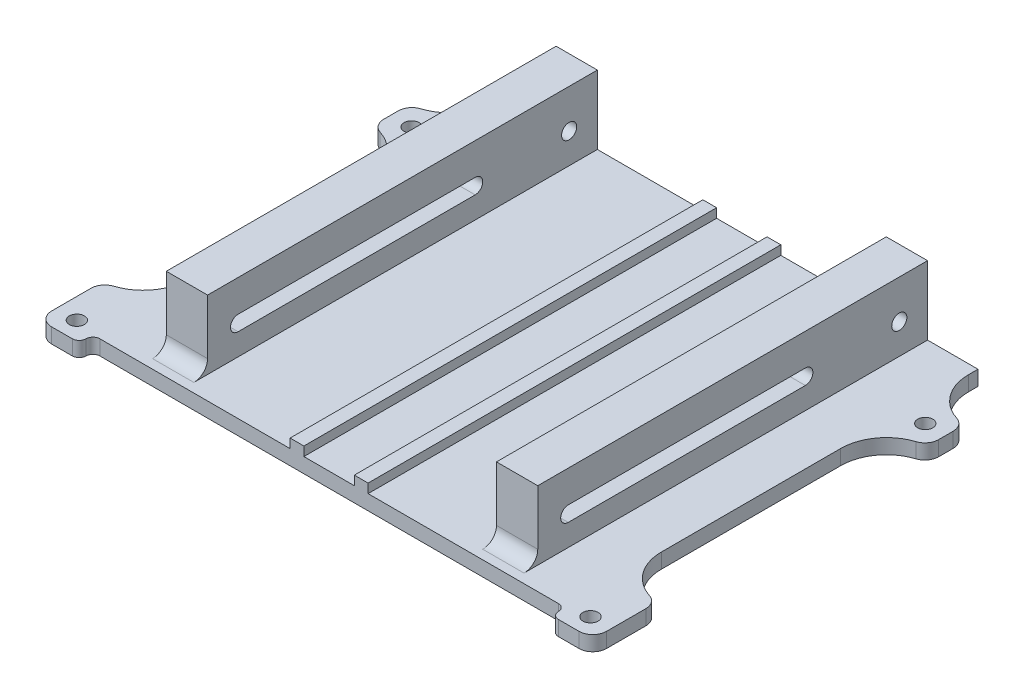
SolidWorks part; units mm, degrees
ref_plane "Front Plane" through (0, 0, 0) normal (0, 0, 1) x (1, 0, 0)
ref_plane "Top Plane" through (0, 0, 0) normal (0, 1, 0) x (1, 0, 0)
ref_plane "Right Plane" through (0, 0, 0) normal (1, 0, 0) x (0, 0, -1)
sketch "Sketch1" plane through (0, 0, 0) normal (0, 1, 0) x (1, 0, 0)
  line L1 (-51.5, 32.5) -> (51.5, 32.5)
  line L2 (-51.5, 32.5) -> (-51.5, -32.5)
  line L3 (-51.5, -32.5) -> (51.5, -32.5)
  line L4 (51.5, 32.5) -> (51.5, -32.5)
  line L5 (-51.5, 32.5) -> (51.5, -32.5) construction
  line L6 (-51.5, -32.5) -> (51.5, 32.5) construction
  point P0 (0, 0)
  dimension "D1" = 65
  dimension "D2" = 103
extrude "Boss-Extrude1" add sketch "Sketch1" along normal blind 3.25
sketch "Sketch2" plane through (0, 3.25, 0) normal (0, 1, 0) x (1, 0, 0)
  line L0 (-51.5, -32.5) -> (51.5, -32.5) construction
  line L1 (-40.5, 32.5) -> (-31.5, 32.5)
  line L2 (-40.5, 32.5) -> (-40.5, -32.5)
  line L3 (-40.5, -32.5) -> (-31.5, -32.5)
  line L4 (-31.5, 32.5) -> (-31.5, -32.5)
  dimension "D1" = 9
  dimension "D2" = 31.5
extrude "Boss-Extrude2" add sketch "Sketch2" along normal blind 15
sketch "Sketch3" plane through (-31.5, 0, 0) normal (1, 0, 0) x (0, 0, -1)
  line L0 (25.85, 9.65) -> (-25.85, 9.65) construction
  line L5 (25.85, 8) -> (-25.85, 8)
  line L6 (25.85, 11.3) -> (-25.85, 11.3)
  arc A4 (25.85, 8) -> (25.85, 11.3) centre (25.85, 9.65) ccw
  arc A5 (-25.85, 11.3) -> (-25.85, 8) centre (-25.85, 9.65) ccw
  point P2 (0, 9.65)
  point P9 (27.5, 11.3)
  point P12 (27.5, 8)
  point P17 (-27.5, 11.3)
  dimension "D4" = 51.7
  dimension "D1" = 3.3
  dimension "D2" = 55
  dimension "D3" = 3.3
extrude "Cut-Extrude1" cut sketch "Sketch3" against normal through all
sketch "Sketch4" plane through (0, 0, -32.5) normal (0, 0, -1) x (-1, 0, 0)
  line L8 (-51.5, 0) -> (51.5, 0)
  line L9 (51.5, 0) -> (51.5, 3.25)
  line L10 (40.5, 18.25) -> (31.5, 18.25)
  line L11 (31.5, 18.25) -> (31.5, 3.25)
  line L12 (31.5, 3.25) -> (-51.5, 3.25)
  line L13 (51.5, 3.25) -> (40.5, 3.25)
  line L14 (51.5, 3.25) -> (40.5, 3.25)
  line L15 (-51.5, 3.25) -> (-51.5, 0)
  line L16 (-51.5, 0) -> (51.5, 0)
  line L17 (51.5, 0) -> (51.5, 3.25)
  line L18 (40.5, 18.25) -> (31.5, 18.25)
  line L19 (31.5, 18.25) -> (31.5, 3.25)
  line L20 (31.5, 3.25) -> (-51.5, 3.25)
  line L23 (-51.5, 3.25) -> (-51.5, 0)
  line L24 (40.5, 3.25) -> (40.5, 18.25)
  line L25 (40.5, 3.25) -> (40.5, 18.25)
  dimension "D1" = 0
extrude "Boss-Extrude3" add sketch "Sketch4" along normal blind 20
sketch "Sketch5" plane through (-31.5, 0, 0) normal (1, 0, 0) x (0, 0, -1)
  line L0 (27.5, 9.8) -> (53.9335, 9.8) construction
  circle A0 centre (46.3391, 9.8) radius 1.65
  dimension "D1" = 3.3
extrude "Cut-Extrude2" cut sketch "Sketch5" against normal through all
mirror "Mirror1" about plane through (0, 0, 0) normal (1, 0, 0) of "Boss-Extrude3", "Boss-Extrude2", "Cut-Extrude1", "Cut-Extrude2"
sketch "Sketch11" plane through (0, 0, 32.5) normal (0, 0, 1) x (1, 0, 0)
  line L0 (35.75, 0) -> (-35.75, 0) construction
  line L1 (-51.5, 0) -> (51.5, 0)
  line L2 (-51.5, 0) -> (-51.5, 3.25)
  line L3 (-51.5, 3.25) -> (51.5, 3.25)
  line L4 (51.5, 0) -> (51.5, 3.25)
  line L5 (51.5, 3.25) -> (51.5, 0) construction
  line L6 (-31.5, 3.25) -> (31.5, 3.25) construction
  line L7 (-51.5, 3.25) -> (-51.5, 0) construction
  dimension "D1" = 0
  dimension "D2" = 0
extrude "Boss-Extrude8" add sketch "Sketch11" along normal blind 5
sketch "Sketch12" plane through (0, 0, 0) normal (0, 1, 0) x (1, 0, 0)
  line L0 (56, -32.5) -> (56, -40.5) construction
  line L1 (51.5, -32.5) -> (60.5, -32.5)
  line L2 (51.5, -32.5) -> (51.5, -40.5)
  line L3 (51.5, -40.5) -> (60.5, -40.5)
  line L4 (60.5, -32.5) -> (60.5, -40.5)
  line L5 (60.5, -36.5) -> (51.5, -36.5) construction
  line L6 (51.5, 40.5) -> (51.5, 32.5)
  line L7 (51.5, 40.5) -> (60.5, 40.5)
  line L8 (60.5, 40.5) -> (60.5, 32.5)
  line L9 (51.5, 32.5) -> (60.5, 32.5)
  line L10 (0, -48.618) -> (0, 67.208) construction
  line L11 (-60.5, -36.5) -> (-51.5, -36.5) construction
  line L12 (-56, -32.5) -> (-56, -40.5) construction
  line L13 (-51.5, 32.5) -> (-60.5, 32.5)
  line L14 (-60.5, 40.5) -> (-60.5, 32.5)
  line L15 (-51.5, 40.5) -> (-60.5, 40.5)
  line L16 (-51.5, 40.5) -> (-51.5, 32.5)
  line L17 (-60.5, -32.5) -> (-60.5, -40.5)
  line L18 (-51.5, -40.5) -> (-60.5, -40.5)
  line L19 (-51.5, -32.5) -> (-51.5, -40.5)
  line L20 (-51.5, -32.5) -> (-60.5, -32.5)
  circle A0 centre (56, -36.5) radius 1.65
  circle A1 centre (56, 36.5) radius 1.65
  circle A2 centre (-56, 36.5) radius 1.65
  circle A3 centre (-56, -36.5) radius 1.65
  dimension "D2" = 0
  dimension "D3" = 3.3
  dimension "D1" = 9
  dimension "D4" = 2
extrude "Boss-Extrude9" add sketch "Sketch12" along normal blind 3.25
sketch "Sketch15" plane through (0, 0, 32.5) normal (0, 0, -1) x (-1, 0, 0)
  line L0 (51.5, 0) -> (60.5, 0) construction
  line L1 (60.5, 0) -> (60.5, 3.25) construction
  line L2 (60.5, 3.25) -> (51.5, 3.25) construction
  line L3 (51.5, 3.25) -> (51.5, 0) construction
  line L4 (-60.5, 0) -> (-51.5, 0) construction
  line L5 (-51.5, 0) -> (-51.5, 3.25) construction
  line L6 (-51.5, 3.25) -> (-60.5, 3.25) construction
  line L7 (-60.5, 3.25) -> (-60.5, 0) construction
  line L8 (51.5, 0) -> (60.5, 0)
  line L9 (60.5, 0) -> (60.5, 3.25)
  line L10 (60.5, 3.25) -> (51.5, 3.25)
  line L11 (51.5, 3.25) -> (51.5, 0)
  line L12 (-60.5, 0) -> (-51.5, 0)
  line L13 (-51.5, 0) -> (-51.5, 3.25)
  line L14 (-51.5, 3.25) -> (-60.5, 3.25)
  line L15 (-60.5, 3.25) -> (-60.5, 0)
extrude "Boss-Extrude10" add sketch "Sketch15" along normal blind 6
fillet "Fillet1" radius 10 6 edges at (51.5, 1.625, 26.5) (51.5, 1.625, -32.5) (51.5, 1.625, -40.5) (-51.5, 1.625, -40.5) (-51.5, 1.625, -32.5) (-51.5, 1.625, 26.5)
fillet "Fillet2" radius 1.5 4 edges at (-51.5, 1.625, 40.5) (-51.5, 1.625, 37.5) (51.5, 1.625, 37.5) (51.5, 1.625, 40.5)
fillet "Fillet3" radius 3 8 edges at (-60.5, 1.625, 40.5) (-60.5, 1.625, 26.5) (-60.5, 1.625, -32.5) (-60.5, 1.625, -40.5) (60.5, 1.625, -32.5) (60.5, 1.625, -40.5) (60.5, 1.625, 26.5) (60.5, 1.625, 40.5)
fillet "Fillet4" radius 3 2 edges at (-36, 3.25, 32.5) (36, 3.25, 32.5)
sketch "Sketch16" plane through (0, 3.25, 0) normal (0, 1, 0) x (1, 0, 0)
  line L0 (0, -39.6632) -> (0, 71.1466) construction
  line L1 (-5.5, 71.1466) -> (-5.5, -54.6537)
  line L2 (-31.5, 52.5) -> (31.5, 52.5) construction
  line L3 (-5.5, 52.5) -> (-8.5, 52.5)
  line L4 (-5.5, 52.5) -> (-5.5, -37.5)
  line L5 (-5.5, -37.5) -> (-8.5, -37.5)
  line L6 (-8.5, 52.5) -> (-8.5, -37.5)
  line L7 (50, -37.5) -> (-50, -37.5) construction
  dimension "D1" = 5.5
  dimension "D2" = 3
extrude "Boss-Extrude11" add sketch "Sketch16" along normal blind 2 contours L6 L5 L4 L3
mirror "Mirror2" about plane through (0, 0, 0) normal (1, 0, 0) of "Boss-Extrude11"
